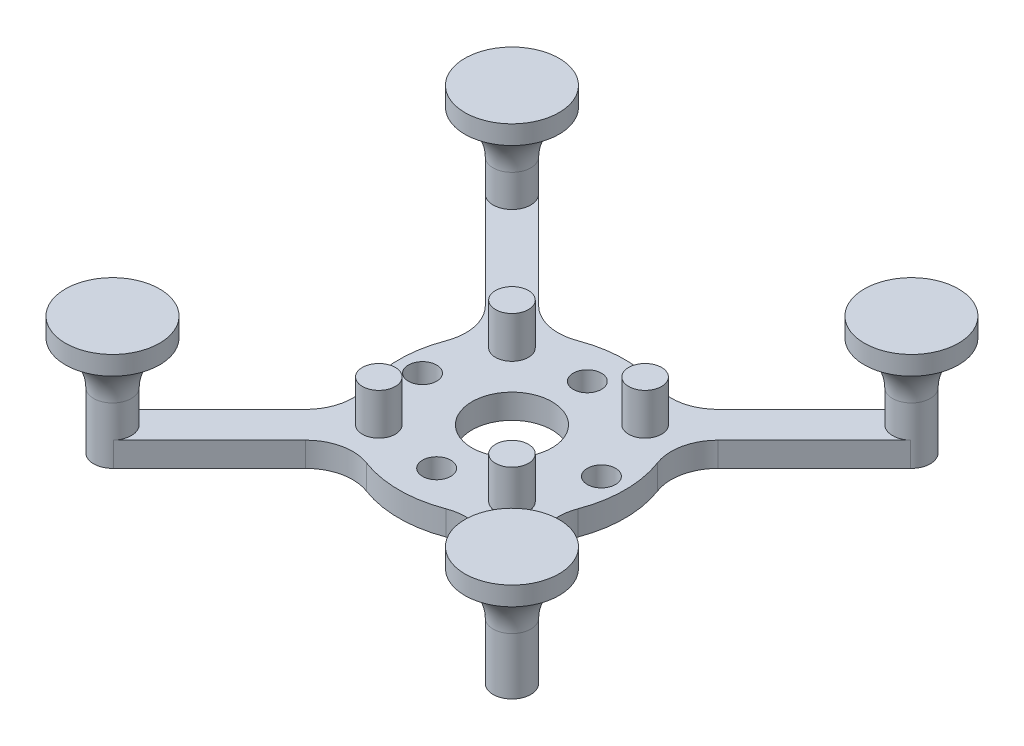
SolidWorks part; units mm, degrees
ref_plane "Front Plane" through (0, 0, 0) normal (0, 0, 1) x (1, 0, 0)
ref_plane "Top Plane" through (0, 0, 0) normal (0, 1, 0) x (1, 0, 0)
ref_plane "Right Plane" through (0, 0, 0) normal (1, 0, 0) x (0, 0, -1)
ref_axis "Axis1" through (-33.0333, 0, 0) along (1, 0, 0)
ref_axis "Axis2" through (0, 24.5224, 0) along (0, -1, 0)
ref_axis "Axis3" through (0, 0, -30.7663) along (0, 0, 1)
sketch "Sketch1" plane through (0, 0, 0) normal (0, 1, 0) x (1, 0, 0)
  line L0 (0, 8) -> (0, -8) construction
  line L1 (-9.5, 0) -> (9.5, 0) construction
  circle A0 centre (0, 0) radius 12
  circle A1 centre (0, 8) radius 1.5
  circle A2 centre (9.5, 0) radius 1.5
  circle A3 centre (0, -8) radius 1.5
  circle A4 centre (-9.5, 0) radius 1.5
  circle A5 centre (0, 0) radius 4.25
  point P7 (0, 0)
  point P8 (0, 0)
  dimension "D1" = 16
  dimension "D2" = 19
  dimension "D3" = 3
  dimension "D4" = 24
  dimension "D5" = 8.5
extrude "Boss-Extrude1" add sketch "Sketch1" along normal blind 2.6
sketch "Sketch2" plane through (0, 2.6, 0) normal (0, 1, 0) x (1, 0, 0)
  line L0 (-7.0711, 7.0711) -> (7.0711, -7.0711) construction
  line L1 (-7.0711, -7.0711) -> (7.0711, 7.0711) construction
  line L2 (0, 0) -> (0, 3.175) construction
  circle A0 centre (0, 0) radius 10 construction
  circle A1 centre (-7.0711, 7.0711) radius 1.75
  circle A2 centre (7.0711, 7.0711) radius 1.75
  circle A3 centre (7.0711, -7.0711) radius 1.75
  circle A4 centre (-7.0711, -7.0711) radius 1.75
  point P7 (0, 0)
  point P8 (0, 0)
  dimension "D1" = 20
  dimension "D3" = 3.5
  dimension "D2" = 45
extrude "Boss-Extrude2" add sketch "Sketch2" along normal blind 4.4
sketch "Sketch3" plane through (0, 2.6, 0) normal (0, 1, 0) x (1, 0, 0)
  line L0 (-21.2132, 21.2132) -> (21.2132, -21.2132) construction
  line L1 (-21.2132, -21.2132) -> (21.2132, 21.2132) construction
  line L2 (0, 0) -> (0, 2.54) construction
  line L3 (-22.5802, 19.7518) -> (-9.7808, 6.9524)
  line L4 (-19.7518, 22.5802) -> (-6.9524, 9.7808)
  line L5 (-16.1805, 13.3521) -> (-13.3521, 16.1805) construction
  line L18 (19.7518, 22.5802) -> (6.9524, 9.7808)
  line L19 (22.5802, 19.7518) -> (9.7808, 6.9524)
  line L20 (22.5802, -19.7518) -> (9.7808, -6.9524)
  line L21 (19.7518, -22.5802) -> (6.9524, -9.7808)
  line L22 (-19.7518, -22.5802) -> (-6.9524, -9.7808)
  line L23 (-22.5802, -19.7518) -> (-9.7808, -6.9524)
  circle A0 centre (0, 0) radius 30 construction
  circle A1 centre (0, 0) radius 12 construction
  arc A5 (-9.7808, 6.9524) -> (-6.9524, 9.7808) centre (2.8584, -2.8584) cw
  arc A12 (-19.7518, 22.5802) -> (-22.5802, 19.7518) centre (-21.2132, 21.2132) ccw
  arc A19 (6.9524, 9.7808) -> (9.7808, 6.9524) centre (-2.8584, -2.8584) cw
  arc A20 (22.5802, 19.7518) -> (19.7518, 22.5802) centre (21.2132, 21.2132) ccw
  arc A21 (9.7808, -6.9524) -> (6.9524, -9.7808) centre (-2.8584, 2.8584) cw
  arc A22 (19.7518, -22.5802) -> (22.5802, -19.7518) centre (21.2132, -21.2132) ccw
  arc A23 (-6.9524, -9.7808) -> (-9.7808, -6.9524) centre (2.8584, 2.8584) cw
  arc A24 (-22.5802, -19.7518) -> (-19.7518, -22.5802) centre (-21.2132, -21.2132) ccw
  point P7 (0, 0)
  point P8 (0, 0)
  point P20 (-14.7663, 14.7663)
  point P36 (0, 0)
  point P39 (2.8584, -2.8584)
  point P43 (0, 0)
  dimension "D1" = 60
  dimension "D3" = 4
  dimension "D2" = 45
extrude "Boss-Extrude3" add sketch "Sketch3" against normal up to surface (2.6 mm away) up to face at (0, 0, 12)
sketch "Sketch5" plane through (0, 2.6, 0) normal (0, 1, 0) x (1, 0, 0)
  circle A4 centre (-21.2132, 21.2132) radius 2.0011
  circle A5 centre (21.2132, 21.2132) radius 2.0011
  circle A6 centre (21.2132, -21.2132) radius 2.0011
  circle A7 centre (-21.2132, -21.2132) radius 2.0011
extrude "Boss-Extrude4" add sketch "Sketch5" along normal blind 10
sketch "Sketch6" plane through (0, 12.6, 0) normal (0, 1, 0) x (1, 0, 0)
  circle A0 centre (21.2132, -21.2132) radius 5
  circle A1 centre (21.2132, 21.2132) radius 5
  circle A2 centre (-21.2132, 21.2132) radius 5
  circle A3 centre (-21.2132, -21.2132) radius 5
  point P12 (20.955, 20.955)
  point P13 (-21.2132, -21.2132)
  point P15 (21.2132, -21.2132)
  point P17 (21.2132, 21.2132)
  dimension "D1" = 10
extrude "Boss-Extrude5" add sketch "Sketch6" against normal blind 2
fillet "Fillet1" radius 5 8 edges at (-6.9524, 1.3, -9.7808) (-9.7808, 1.3, -6.9524) (-9.7808, 1.3, 6.9524) (9.7808, 1.3, 6.9524) (-6.9524, 1.3, 9.7808) (6.9524, 1.3, 9.7808) (9.7808, 1.3, -6.9524) (6.9524, 1.3, -9.7808)
fillet "Fillet2" radius 5 4 edges at (-21.2132, 10.6, -19.2121) (-21.2132, 10.6, 23.2143) (21.2132, 10.6, 23.2143) (21.2132, 10.6, -19.2121)
